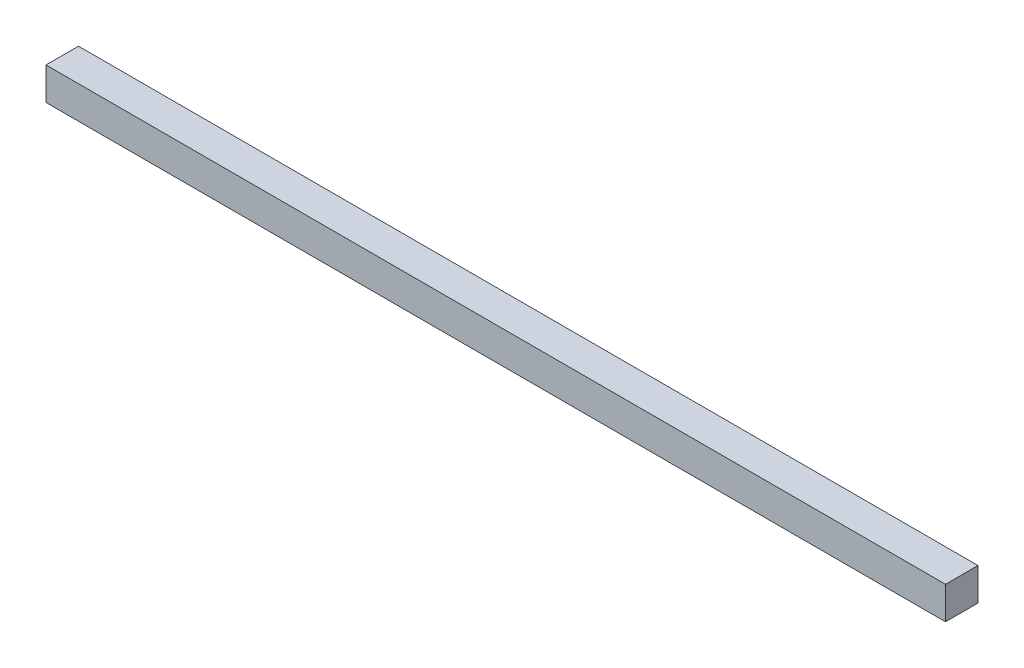
SolidWorks part; units mm, degrees
material "Сосна"
ref_plane "Спереди" through (0, 0, 0) normal (0, 0, 1) x (1, 0, 0)
ref_plane "Сверху" through (0, 0, 0) normal (0, 1, 0) x (1, 0, 0)
ref_plane "Справа" through (0, 0, 0) normal (1, 0, 0) x (0, 0, -1)
sketch "Эскиз1" plane through (0, 0, 0) normal (0, 1, 0) x (1, 0, 0)
  line L1 (0, 15) -> (415, 15)
  line L2 (0, 15) -> (0, 0)
  line L3 (0, 0) -> (415, 0)
  line L4 (415, 15) -> (415, 0)
  dimension "D1" = 15
  dimension "D2" = 415
extrude "Бобышка-Вытянуть1" add sketch "Эскиз1" along normal blind 15
